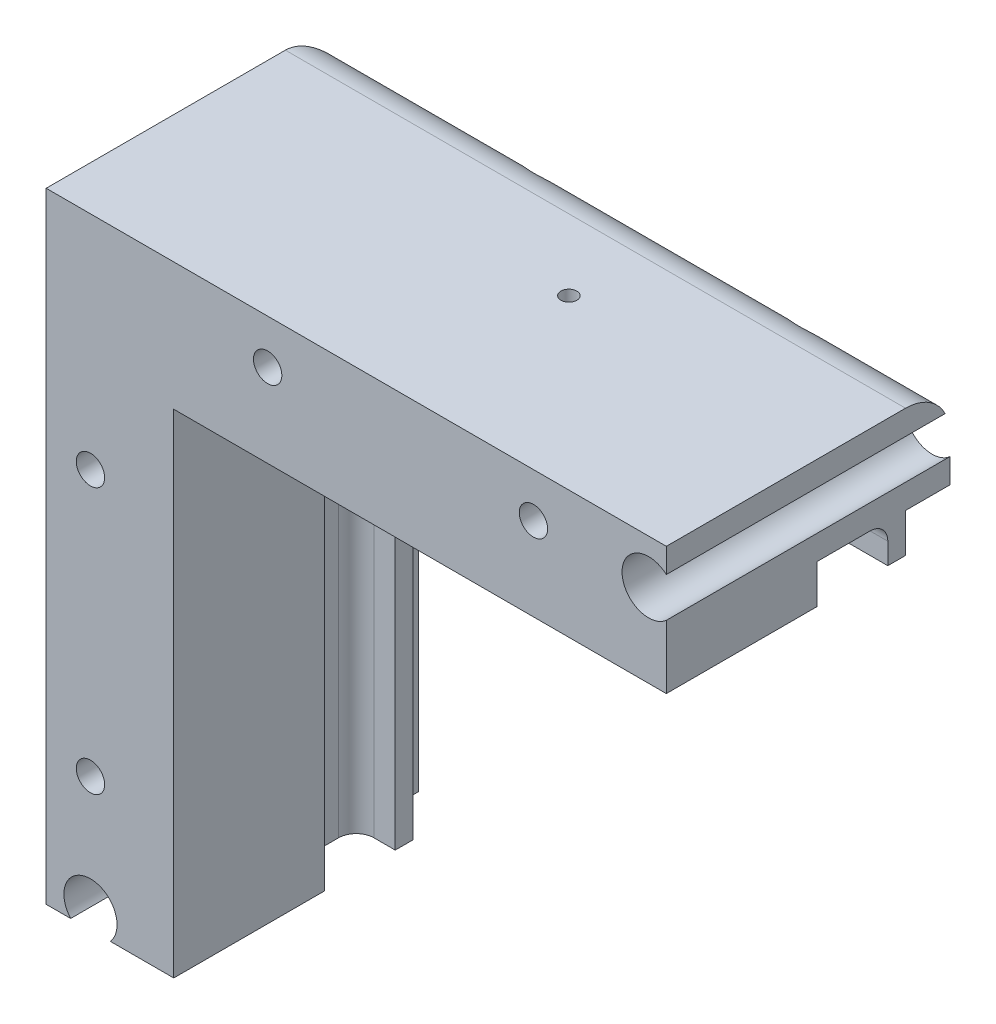
SolidWorks part; units mm, degrees
ref_plane "Front Plane" through (0, 0, 0) normal (0, 0, 1) x (1, 0, 0)
ref_plane "Top Plane" through (0, 0, 0) normal (0, 1, 0) x (1, 0, 0)
ref_plane "Right Plane" through (0, 0, 0) normal (1, 0, 0) x (0, 0, -1)
sketch "Sketch2" plane through (0, 0, 0) normal (0, 1, 0) x (1, 0, 0)
  line L1 (0, 0) -> (18.288, 0)
  line L2 (0, 0) -> (0, 40.64)
  line L3 (0, 40.64) -> (18.288, 40.64)
  line L4 (18.288, 0) -> (18.288, 40.64)
  dimension "D1" = 40.64
  dimension "D2" = 18.288
extrude "Boss-Extrude1" add sketch "Sketch2" along normal blind 88.9
sketch "Sketch3" plane through (18.288, 0, 0) normal (1, 0, 0) x (0, 0, -1)
  line L0 (40.64, 88.9) -> (40.64, 0) construction
  line L1 (0, 88.9) -> (40.64, 88.9)
  line L2 (0, 88.9) -> (0, 70.612)
  line L3 (0, 70.612) -> (40.64, 70.612)
  line L4 (40.64, 88.9) -> (40.64, 70.612)
  dimension "D1" = 18.288
extrude "Boss-Extrude2" add sketch "Sketch3" along normal blind 70.612
sketch "Sketch4" plane through (88.9, 0, 0) normal (1, 0, 0) x (0, 0, -1)
  line L0 (40.64, 88.9) -> (0, 88.9) construction
  line L1 (40.64, 70.612) -> (34.29, 70.612)
  line L2 (40.64, 70.612) -> (40.64, 76.2)
  line L3 (40.64, 76.2) -> (34.29, 76.2)
  line L4 (34.29, 70.612) -> (34.29, 76.2)
  line L6 (31.75, 70.612) -> (21.59, 70.612)
  line L7 (31.75, 70.612) -> (31.75, 76.2)
  line L8 (31.75, 76.2) -> (21.59, 76.2)
  line L9 (21.59, 70.612) -> (21.59, 76.2)
  dimension "D1" = 6.35
  dimension "D2" = 12.7
  dimension "D3" = 2.54
  dimension "D4" = 10.16
  dimension "D5" = 12.7
extrude "Cut-Extrude1" cut sketch "Sketch4" against normal blind 76.2
sketch "Sketch5" plane through (0, 0, 0) normal (0, -1, 0) x (1, 0, 0)
  line L0 (18.288, 0) -> (18.288, -40.64) construction
  line L1 (18.288, -40.64) -> (12.7, -40.64)
  line L2 (18.288, -40.64) -> (18.288, -34.29)
  line L3 (18.288, -34.29) -> (12.7, -34.29)
  line L4 (12.7, -40.64) -> (12.7, -34.29)
  line L5 (18.288, -31.75) -> (12.7, -31.75)
  line L6 (18.288, -31.75) -> (18.288, -21.59)
  line L7 (18.288, -21.59) -> (12.7, -21.59)
  line L8 (12.7, -31.75) -> (12.7, -21.59)
  line L9 (0, -40.64) -> (0, 0) construction
  dimension "D1" = 6.35
  dimension "D2" = 12.7
  dimension "D3" = 12.7
  dimension "D4" = 2.54
  dimension "D5" = 10.16
extrude "Cut-Extrude2" cut sketch "Sketch5" against normal blind 76.2
sketch "Sketch6" plane through (0, 0, -40.64) normal (0, 0, -1) x (-1, 0, 0)
  line L0 (-88.9, 82.55) -> (0, 82.55) construction
  line L1 (-88.9, 76.2) -> (-88.9, 88.9) construction
  line L2 (0, 88.9) -> (0, 0) construction
  line L3 (-6.35, 0) -> (-6.35, 88.9) construction
  line L4 (-12.7, 0) -> (0, 0) construction
  line L5 (-88.9, 88.9) -> (0, 88.9) construction
  line L6 (-12.7, 76.2) -> (0, 76.2) construction
  line L7 (-12.7, 88.9) -> (-12.7, 76.2) construction
  line L8 (-50.8, 76.2) -> (-50.8, 88.9) construction
  line L9 (-12.7, 76.2) -> (-88.9, 76.2) construction
  line L10 (-12.7, 38.1) -> (0, 38.1) construction
  line L12 (-12.7, 0) -> (-12.7, 76.2) construction
  line L13 (-88.9, 76.2) -> (-50.8, 76.2) construction
  line L14 (-50.8, 76.2) -> (-12.7, 76.2) construction
  line L15 (-12.7, 76.2) -> (-12.7, 38.1) construction
  line L16 (-12.7, 38.1) -> (-12.7, 0) construction
  line L17 (-12.7, 0) -> (0, 0) construction
  line L18 (0, 0) -> (0, 38.1) construction
  line L19 (0, 38.1) -> (0, 76.2) construction
  line L20 (0, 76.2) -> (0, 88.9) construction
  line L21 (0, 88.9) -> (-12.7, 88.9) construction
  line L22 (-12.7, 88.9) -> (-50.8, 88.9) construction
  line L23 (-50.8, 88.9) -> (-88.9, 88.9) construction
  line L24 (-88.9, 88.9) -> (-88.9, 76.2) construction
  line L25 (-69.85, 76.2) -> (-69.85, 88.9) construction
  line L26 (-31.75, 76.2) -> (-31.75, 88.9) construction
  line L27 (-12.7, 57.15) -> (0, 57.15) construction
  line L28 (-12.7, 19.05) -> (0, 19.05) construction
  circle A0 centre (-6.35, 19.05) radius 5.08
  circle A1 centre (-6.35, 57.15) radius 5.08
  circle A2 centre (-31.75, 82.55) radius 5.08
  circle A3 centre (-69.85, 82.55) radius 5.08
  dimension "D3" = 10.16
  dimension "D4" = 10.16
  dimension "D5" = 10.16
  dimension "D6" = 10.16
  dimension "D1" = 38.1
  dimension "D2" = 38.1
extrude "Cut-Extrude3" cut sketch "Sketch6" against normal offset from surface (15.24 mm away) 25.4 up to face at (35.7293, 53.1707, 0)
sketch "Sketch7" plane through (0, 0, -40.64) normal (0, 0, -1) x (-1, 0, 0)
  circle A0 centre (-69.85, 82.55) radius 2.032
  circle A1 centre (-6.35, 57.15) radius 2.032
  circle A2 centre (-31.75, 82.55) radius 2.032
  circle A3 centre (-6.35, 19.05) radius 2.032
  dimension "D1" = 4.064
  dimension "D2" = 4.064
  dimension "D3" = 4.064
  dimension "D4" = 4.064
extrude "Cut-Extrude4" cut sketch "Sketch7" against normal through all
fillet "Fillet1" radius 2.54 2 edges at (12.7, 38.1, -31.75) (50.8, 76.2, -31.75)
fillet "Fillet2" radius 6.35 2 edges at (0, 44.45, -40.64) (44.45, 88.9, -40.64)
sketch "Sketch8" plane through (0, 0, 0) normal (0, 0, 1) x (1, 0, 0)
  line L0 (88.9, 82.55) -> (0, 82.55) construction
  line L1 (88.9, 88.9) -> (88.9, 70.612) construction
  line L2 (0, 88.9) -> (0, 0) construction
  line L3 (6.35, 0) -> (6.35, 88.9) construction
  line L4 (0, 0) -> (18.288, 0) construction
  line L5 (0, 88.9) -> (88.9, 88.9) construction
  circle A0 centre (6.35, 2.54) radius 3.81
  circle A1 centre (86.36, 82.55) radius 3.81
  dimension "D1" = 7.62
  dimension "D3" = 7.62
  dimension "D2" = 2.54
  dimension "D4" = 2.54
  dimension "D5" = 6.35
  dimension "D6" = 6.35
extrude "Cut-Extrude5" cut sketch "Sketch8" against normal through all
sketch "Sketch9" plane through (0, 76.2, 0) normal (0, -1, 0) x (1, 0, 0)
  line L0 (50.8, -21.59) -> (50.8, -29.21) construction
  line L1 (12.7, -21.59) -> (88.9, -21.59) construction
  line L2 (12.7, -29.21) -> (88.9, -29.21) construction
  circle A0 centre (50.8, -24.13) radius 1.143
  dimension "D1" = 2.286
  dimension "D2" = 2.54
extrude "Cut-Extrude6" cut sketch "Sketch9" against normal up to next
sketch "Sketch10" plane through (12.7, 0, 0) normal (1, 0, 0) x (0, 0, -1)
  line L0 (21.59, 38.1) -> (29.21, 38.1) construction
  line L1 (21.59, 76.2) -> (21.59, 0) construction
  line L2 (29.21, 0) -> (29.21, 76.2) construction
  circle A0 centre (24.13, 38.1) radius 1.143
  dimension "D1" = 2.286
  dimension "D2" = 2.54
extrude "Cut-Extrude7" cut sketch "Sketch10" against normal up to next
